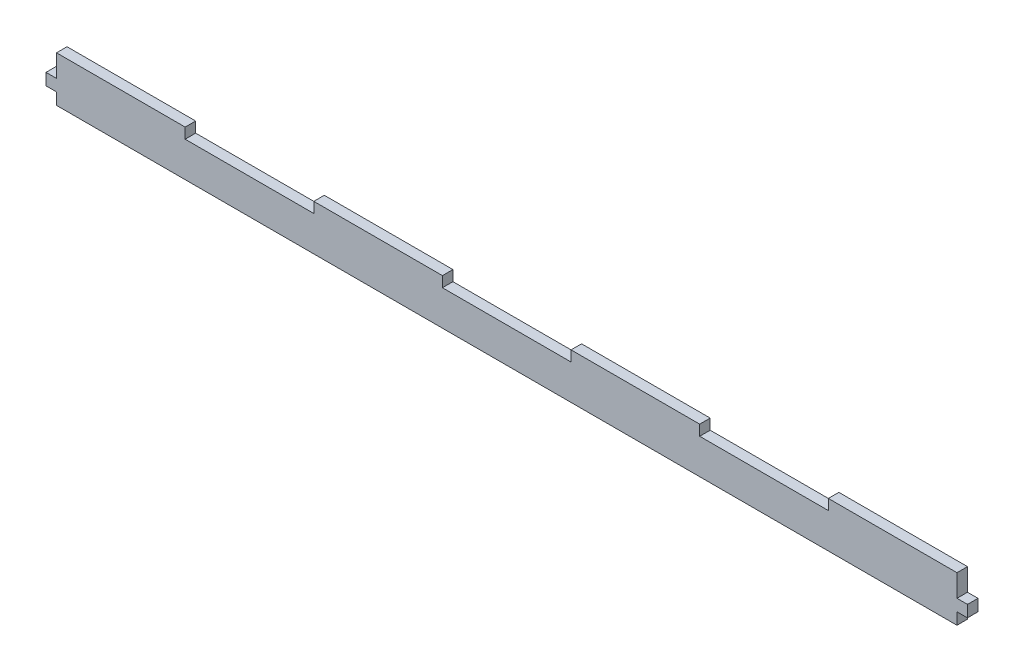
SolidWorks part; units mm, degrees
ref_plane "Front Plane" through (0, 0, 0) normal (0, 0, 1) x (1, 0, 0)
ref_plane "Top Plane" through (0, 0, 0) normal (0, 1, 0) x (1, 0, 0)
ref_plane "Right Plane" through (0, 0, 0) normal (1, 0, 0) x (0, 0, -1)
sketch "Sketch1" plane through (0, 0, 0) normal (0, 1, 0) x (1, 0, 0)
  line L1 (-233, -63.25) -> (233, -63.25)
  line L2 (-233, -63.25) -> (-233, 63.25)
  line L3 (-233, 63.25) -> (233, 63.25)
  line L4 (233, -63.25) -> (233, 63.25)
  line L5 (-233, -63.25) -> (233, 63.25) construction
  line L6 (-233, 63.25) -> (233, -63.25) construction
  point P0 (0, 0)
  dimension "D1" = 126.5
  dimension "D2" = 466
extrude "Boss-Extrude1" add sketch "Sketch1" along normal blind 6
sketch "Sketch2" plane through (0, 6, 0) normal (0, 1, 0) x (1, 0, 0)
  line L0 (239, -69.25) -> (239, 69.25)
  line L3 (-239, -69.25) -> (239, -69.25)
  line L4 (233, -63.25) -> (233, 63.25)
  line L5 (233, 63.25) -> (-233, 63.25)
  line L6 (-233, 63.25) -> (-233, -63.25)
  line L7 (-233, -63.25) -> (233, -63.25)
  line L8 (233, -63.25) -> (233, 63.25)
  line L9 (233, 63.25) -> (-233, 63.25)
  line L10 (-233, 63.25) -> (-233, -63.25)
  line L11 (-233, -63.25) -> (233, -63.25)
  line L12 (257, -87.25) -> (257, 87.25)
  line L13 (257, 87.25) -> (-257, 87.25)
  line L14 (-257, 87.25) -> (-257, -87.25)
  line L15 (-257, -87.25) -> (257, -87.25)
  line L16 (263, -93.25) -> (263, 93.25)
  line L19 (-263, -93.25) -> (263, -93.25)
  line L20 (239, 69.25) -> (-239, 69.25) construction
  line L21 (-239, 69.25) -> (-239, -69.25) construction
  line L22 (-239, -69.25) -> (-239, -63.25)
  line L27 (170.7143, 69.25) -> (102.4286, 69.25)
  line L28 (170.7143, 69.25) -> (170.7143, 63.25)
  line L29 (170.7143, 63.25) -> (102.4286, 63.25)
  line L30 (102.4286, 69.25) -> (102.4286, 63.25)
  line L31 (102.4286, 69.25) -> (34.1429, 69.25)
  line L32 (102.4286, 69.25) -> (102.4286, 63.25)
  line L33 (102.4286, 63.25) -> (34.1429, 63.25)
  line L34 (34.1429, 69.25) -> (34.1429, 63.25)
  line L35 (34.1429, 69.25) -> (-34.1429, 69.25)
  line L36 (34.1429, 69.25) -> (34.1429, 63.25)
  line L37 (34.1429, 63.25) -> (-34.1429, 63.25)
  line L38 (-34.1429, 69.25) -> (-34.1429, 63.25)
  line L39 (-34.1429, 69.25) -> (-102.4286, 69.25)
  line L40 (-34.1429, 69.25) -> (-34.1429, 63.25)
  line L41 (-34.1429, 63.25) -> (-102.4286, 63.25)
  line L42 (-102.4286, 69.25) -> (-102.4286, 63.25)
  line L43 (-102.4286, 69.25) -> (-170.7143, 69.25)
  line L44 (-102.4286, 69.25) -> (-102.4286, 63.25)
  line L45 (-102.4286, 63.25) -> (-170.7143, 63.25)
  line L46 (-170.7143, 69.25) -> (-170.7143, 63.25)
  line L47 (-170.7143, 69.25) -> (-239, 69.25)
  line L48 (-170.7143, 69.25) -> (-170.7143, 63.25)
  line L49 (-170.7143, 63.25) -> (-239, 63.25)
  line L50 (-239, 69.25) -> (-239, 63.25)
  line L51 (-239, 63.25) -> (-233, 63.25)
  line L52 (-239, 63.25) -> (-239, 37.95)
  line L53 (-239, 37.95) -> (-233, 37.95)
  line L54 (-233, 63.25) -> (-233, 37.95)
  line L55 (-233, 37.95) -> (-239, 37.95)
  line L56 (-233, 37.95) -> (-233, 12.65)
  line L57 (-233, 12.65) -> (-239, 12.65)
  line L58 (-239, 37.95) -> (-239, 12.65)
  line L59 (-239, 12.65) -> (-233, 12.65)
  line L60 (-239, 12.65) -> (-239, -12.65)
  line L61 (-239, -12.65) -> (-233, -12.65)
  line L62 (-233, 12.65) -> (-233, -12.65)
  line L63 (-233, -12.65) -> (-239, -12.65)
  line L64 (-233, -12.65) -> (-233, -37.95)
  line L65 (-233, -37.95) -> (-239, -37.95)
  line L66 (-239, -12.65) -> (-239, -37.95)
  line L67 (-239, -37.95) -> (-233, -37.95)
  line L68 (-239, -37.95) -> (-239, -63.25)
  line L69 (-239, -63.25) -> (-233, -63.25)
  line L70 (-233, -37.95) -> (-233, -63.25)
  line L71 (170.7143, 63.25) -> (239, 63.25)
  line L72 (170.7143, 63.25) -> (170.7143, 69.25)
  line L73 (170.7143, 69.25) -> (239, 69.25)
  line L74 (239, 63.25) -> (239, 69.25)
  line L75 (-263, 93.25) -> (-257, 93.25)
  line L76 (-263, 93.25) -> (-263, 55.95)
  line L77 (-263, 55.95) -> (-257, 55.95)
  line L78 (-257, 93.25) -> (-257, 55.95)
  line L79 (-263, 93.25) -> (-263, -93.25) construction
  line L80 (-257, 55.95) -> (-263, 55.95)
  line L81 (-257, 55.95) -> (-257, 18.65)
  line L82 (-257, 18.65) -> (-263, 18.65)
  line L83 (-263, 55.95) -> (-263, 18.65)
  line L84 (-263, 18.65) -> (-257, 18.65)
  line L85 (-263, 18.65) -> (-263, -18.65)
  line L86 (-263, -18.65) -> (-257, -18.65)
  line L87 (-257, 18.65) -> (-257, -18.65)
  line L88 (-257, -18.65) -> (-263, -18.65)
  line L89 (-257, -18.65) -> (-257, -55.95)
  line L90 (-257, -55.95) -> (-263, -55.95)
  line L91 (-263, -18.65) -> (-263, -55.95)
  line L92 (-263, -55.95) -> (-257, -55.95)
  line L93 (-263, -55.95) -> (-263, -93.25)
  line L94 (-263, -93.25) -> (-257, -93.25)
  line L95 (-257, -55.95) -> (-257, -93.25)
  line L96 (257, 87.25) -> (183.5714, 87.25)
  line L97 (257, 87.25) -> (257, 93.25)
  line L98 (257, 93.25) -> (183.5714, 93.25)
  line L99 (183.5714, 87.25) -> (183.5714, 93.25)
  line L100 (183.5714, 93.25) -> (110.1429, 93.25)
  line L101 (183.5714, 93.25) -> (183.5714, 87.25)
  line L102 (183.5714, 87.25) -> (110.1429, 87.25)
  line L103 (110.1429, 93.25) -> (110.1429, 87.25)
  line L104 (110.1429, 87.25) -> (36.7143, 87.25)
  line L105 (110.1429, 87.25) -> (110.1429, 93.25)
  line L106 (110.1429, 93.25) -> (36.7143, 93.25)
  line L107 (36.7143, 87.25) -> (36.7143, 93.25)
  line L108 (36.7143, 93.25) -> (-36.7143, 93.25)
  line L109 (36.7143, 93.25) -> (36.7143, 87.25)
  line L110 (36.7143, 87.25) -> (-36.7143, 87.25)
  line L111 (-36.7143, 93.25) -> (-36.7143, 87.25)
  line L112 (-36.7143, 87.25) -> (-110.1429, 87.25)
  line L113 (-36.7143, 87.25) -> (-36.7143, 93.25)
  line L114 (-36.7143, 93.25) -> (-110.1429, 93.25)
  line L115 (-110.1429, 87.25) -> (-110.1429, 93.25)
  line L116 (-110.1429, 93.25) -> (-183.5714, 93.25)
  line L117 (-110.1429, 93.25) -> (-110.1429, 87.25)
  line L118 (-110.1429, 87.25) -> (-183.5714, 87.25)
  line L119 (-183.5714, 93.25) -> (-183.5714, 87.25)
  line L120 (-183.5714, 87.25) -> (-257, 87.25)
  line L121 (-183.5714, 87.25) -> (-183.5714, 93.25)
  line L122 (-183.5714, 93.25) -> (-257, 93.25)
  line L123 (-257, 87.25) -> (-257, 93.25)
  line L124 (263, 93.25) -> (-263, 93.25) construction
  line L125 (263, 93.25) -> (257, 93.25)
  dimension "D1" = 0
  dimension "D2" = 6
  dimension "D3" = 18
  dimension "D4" = 6
extrude "Boss-Extrude2" add sketch "Sketch2" against normal blind 20 contours L119 L122 L78 L13 | L116 L119 L13 L115 | L115 L13 L111 L114 | L108 L111 L13 L107 | L107 L13 L103 L106 | L100 L103 L13 L99 | L99 L13 L97 L98 region at (220.2857, 6, -90.25) region at (146.8571, 6, -90.25) region at (73.4286, 6, -90.25) region at (0, 6, -90.25) region at (-73.4286, 6, -90.25) region at (-146.8571, 6, -90.25) region at (-220.2857, 6, -90.25)
extrude "Cut-Extrude1" cut sketch "Sketch1<2>" against normal through all both and the other way through all
sketch "Sketch1<2>" plane through (0, 0, 0) normal (0, 1, 0) x (1, 0, 0) same geometry as "Sketch1"
extrude "Boss-Extrude3" add sketch "Sketch2<4>" along normal blind 6 contours L119 L122 L78 L13 | L115 L13 L111 L114 | L107 L13 L103 L106 | L99 L13 L97 L98 region at (220.2857, 6, -90.25) region at (73.4286, 6, -90.25) region at (-73.4286, 6, -90.25) region at (-220.2857, 6, -90.25)
sketch "Sketch2<4>" plane through (0, 6, 0) normal (0, 1, 0) x (1, 0, 0) same geometry as "Sketch2"
sketch "Sketch4" plane through (-257, 0, 0) normal (-1, 0, 0) x (0, 0, 1)
  line L0 (-93.25, -14) -> (-93.25, 12) construction
  line L1 (-87.25, -14) -> (-93.25, -14)
  line L2 (-87.25, -14) -> (-87.25, -7.3333)
  line L3 (-87.25, -7.3333) -> (-93.25, -7.3333)
  line L4 (-93.25, -14) -> (-93.25, -7.3333)
  line L5 (-87.25, -14) -> (-87.25, 12) construction
  line L6 (-93.25, -7.3333) -> (-87.25, -7.3333)
  line L7 (-93.25, -7.3333) -> (-93.25, -0.6667)
  line L8 (-93.25, -0.6667) -> (-87.25, -0.6667)
  line L9 (-87.25, -7.3333) -> (-87.25, -0.6667)
  line L10 (-93.25, 6) -> (-55.95, 6) construction
  line L11 (-87.25, -0.6667) -> (-93.25, -0.6667)
  line L12 (-87.25, -0.6667) -> (-87.25, 6)
  line L13 (-87.25, 6) -> (-93.25, 6)
  line L14 (-93.25, -0.6667) -> (-93.25, 6)
  line M7 (-87.25, -14) -> (-87.25, 12)
  line M9 (-93.25, 12) -> (-93.25, -14)
extrude "Boss-Extrude4" add sketch "Sketch4" along normal blind 6 contours L8 L3 M9 M7 region at (-257, -4, -90.25)
mirror "Mirror2" about plane through (0, 0, 0) normal (1, 0, 0) of "Boss-Extrude4"
